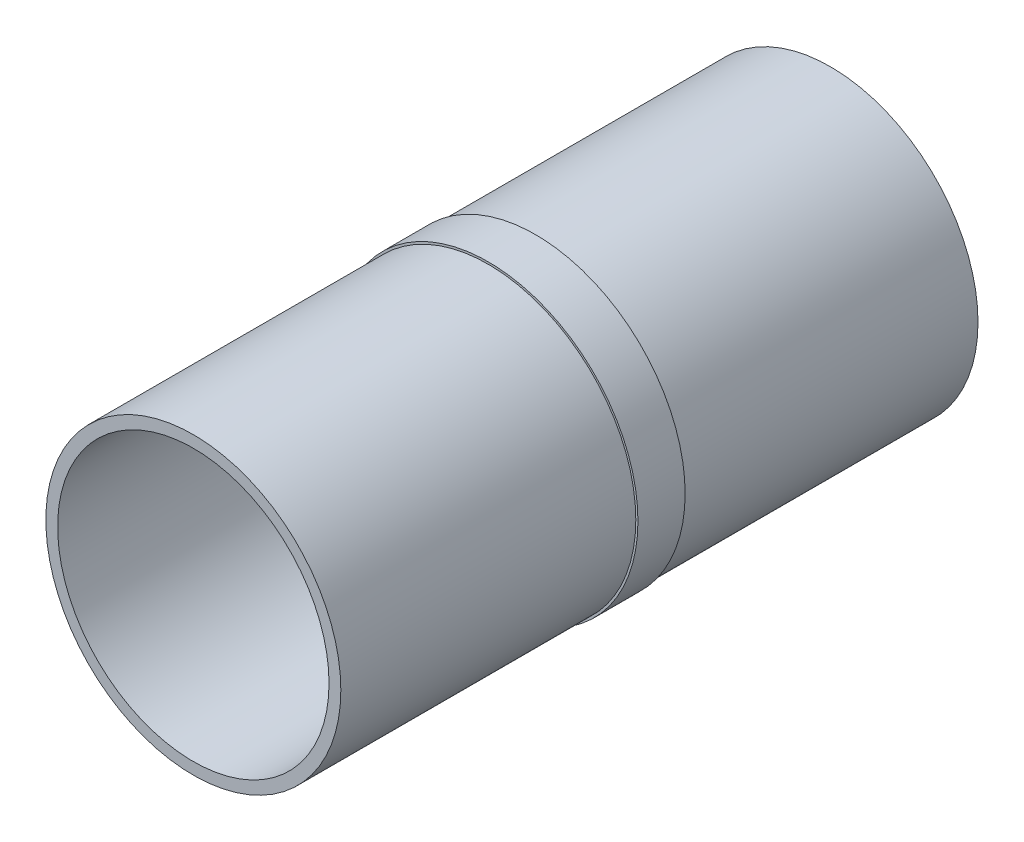
SolidWorks part; units mm, degrees
ref_plane "Front Plane" through (0, 0, 0) normal (0, 0, 1) x (1, 0, 0)
ref_plane "Top Plane" through (0, 0, 0) normal (0, 1, 0) x (1, 0, 0)
ref_plane "Right Plane" through (0, 0, 0) normal (1, 0, 0) x (0, 0, -1)
sketch "Sketch1" plane through (0, 0, 0) normal (0, 0, 1) x (1, 0, 0)
  circle A0 centre (0, 0) radius 79.375
  circle A1 centre (0, 0) radius 73.025
  dimension "D1" = 158.75
  dimension "D2" = 6.35
extrude "Boss-Extrude1" add sketch "Sketch1" along normal blind 342.9
ref_plane "Plane1" through (0, 0, 171.45) normal (0, 0, 1) x (1, 0, 0)
sketch "Sketch2" plane through (0, 0, 171.45) normal (0, 0, 1) x (1, 0, 0)
  circle A0 centre (0, 0) radius 79.375 construction
  circle A1 centre (0, 0) radius 79.375
  circle A2 centre (0, 0) radius 80.518
extrude "Boss-Extrude2" add sketch "Sketch2" against normal mid plane 25.4
